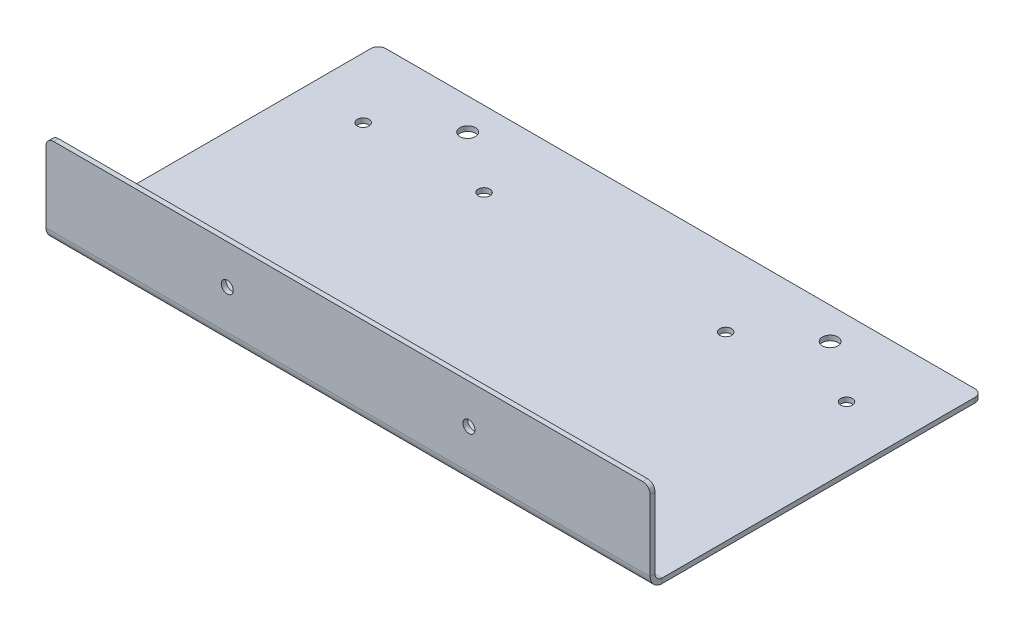
SolidWorks part; units mm, degrees
note: The reader was unsure of these and kept them because the rebuilt part matched: flange length of "Edge-Flange1".
material "5052-O"
ref_plane "Front Plane" through (0, 0, 0) normal (0, 0, 1) x (1, 0, 0)
ref_plane "Top Plane" through (0, 0, 0) normal (0, 1, 0) x (1, 0, 0)
ref_plane "Right Plane" through (0, 0, 0) normal (1, 0, 0) x (0, 0, -1)
sketch "Sketch1" plane through (0, 0, 0) normal (0, 1, 0) x (1, 0, 0)
  line L1 (0, 0) -> (254, 0)
  line L2 (0, 0) -> (0, 139.7)
  line L3 (0, 139.7) -> (254, 139.7)
  line L4 (254, 0) -> (254, 139.7)
  dimension "D1" = 139.7
  dimension "D2" = 254
base flange "Base-Flange1" sketch "Sketch1" thickness 2.0526 reverse thickness direction no parameters "D1"=3
edge flange "Edge-Flange1" sketch "Sketch8" flange angle 90 flange length 38.1 flange position material inside bend radius 3 thickness 2.0526 relief rectangular parameters "D1"=3.175, "D6"=10
sketch "Sketch8" plane through (0, 0, 0) normal (0, 0, 1) x (1, 0, 0)
  line L0 (0, 0) -> (254, 0) construction
  line L1 (0, 0) -> (254, 0)
  line L2 (0, 0) -> (0, 36.0474)
  line L3 (0, 36.0474) -> (254, 36.0474)
  line L4 (254, 36.0474) -> (254, 0)
bend "EdgeBend1" bend radius 3 bend angle 90 parameters "D5"=1
hole_wizard "#8 (0.199) Diameter Hole1" positions "Sketch9" profile "Sketch10" hole size "#8" standard "ANSI Inch" end condition through all
sketch "Sketch9" plane through (0, 0, -2.0526) normal (0, 0, -1) x (-1, 0, 0)
  line L0 (0, 19.5237) -> (-254, 19.5237) construction
  line L1 (0, 36.0474) -> (0, 3) construction
  line L2 (-254, 3) -> (-254, 36.0474) construction
  point P0 (-177.8, 19.5237)
  point P2 (-76.2, 19.5237)
  dimension "D1" = 76.2
  dimension "D2" = 76.2
sketch "Sketch10" plane through (177.8, 19.5237, -2.0526) normal (1, 0, 0) x (0, 1, 0)
  line L0 (0, 0) -> (0, 2.0526)
  line L1 (0, 2.0526) -> (2.5273, 2.0526)
  line L2 (2.5273, 2.0526) -> (2.5273, 0)
  line L5 (2.5273, 0) -> (0, 0)
  line L11 (0, -6.35) -> (0, 107.95) construction
  dimension "Thru Hole Dia." = 5.0546
  dimension "Thru Hole Depth" = 2.0526
hole_wizard "#10 (0.1935) Diameter Hole1" positions "Sketch11" profile "Sketch12" hole size "#10" standard "ANSI Inch" end condition through all
sketch "Sketch11" plane through (0, 0, 0) normal (0, 1, 0) x (1, 0, 0)
  line L0 (0, 107.95) -> (254, 107.95) construction
  line L1 (0, 139.7) -> (0, 5.0526) construction
  line L2 (254, 5.0526) -> (254, 139.7) construction
  line L4 (254, 139.7) -> (0, 139.7) construction
  line L5 (127, 139.7) -> (127, 127.3255) construction
  point P0 (25.4, 107.95)
  point P2 (76.2, 107.95)
  point P4 (177.8, 107.95)
  point P6 (228.6, 107.95)
  dimension "D1" = 31.75
  dimension "D2" = 25.4
  dimension "D3" = 25.4
  dimension "D4" = 50.8
  dimension "D5" = 50.8
sketch "Sketch12" plane through (25.4, 0, -107.95) normal (1, 0, 0) x (0, 0, 1)
  line L0 (0, 0) -> (0, 2.0526)
  line L1 (0, 2.0526) -> (2.4574, 2.0526)
  line L2 (2.4574, 2.0526) -> (2.4574, 0)
  line L5 (2.4574, 0) -> (0, 0)
  line L11 (0, -6.35) -> (0, 107.95) construction
  dimension "Thru Hole Dia." = 4.9149
  dimension "Thru Hole Depth" = 2.0526
hole_wizard "F (0.257) Diameter Hole1" positions "Sketch13" profile "Sketch14" hole size "F" standard "ANSI Inch" end condition through all
sketch "Sketch13" plane through (0, 0, 0) normal (0, 1, 0) x (1, 0, 0)
  line L0 (254, 139.7) -> (0, 139.7) construction
  line L1 (254, 5.0526) -> (254, 139.7) construction
  line L2 (0, 139.7) -> (0, 5.0526) construction
  point P0 (203.2, 126.4818)
  point P7 (50.8, 126.4818)
  point P10 (0, 0)
  dimension "D1" = 13.2182
  dimension "D2" = 50.8
  dimension "D3" = 50.8
sketch "Sketch14" plane through (203.2, 0, -126.4818) normal (1, 0, 0) x (0, 0, 1)
  line L0 (0, 0) -> (0, 2.0526)
  line L1 (0, 2.0526) -> (3.2639, 2.0526)
  line L2 (3.2639, 2.0526) -> (3.2639, 0)
  line L5 (3.2639, 0) -> (0, 0)
  line L11 (0, -6.35) -> (0, 107.95) construction
  dimension "Thru Hole Dia." = 6.5278
  dimension "Thru Hole Depth" = 2.0526
fillet "Fillet1" radius 3.175 4 edges at (254, 36.0474, -1.0263) (254, -1.0263, -139.7) (0, -1.0263, -139.7) (0, 36.0474, -1.0263)
sketch "Bend-Lines1" [suppressed] plane through (0, 0, 0) normal (0, 1, 0) x (1, 0, 0)
sketch "Bounding-Box1" [suppressed] plane through (0, 0, 0) normal (0, 1, 0) x (1, 0, 0)
sheet metal parameters "Sheet-Metal1" thickness 2.0526 parameters "D1"=3.175
flat pattern "Flat-Pattern1" [suppressed]
sketch "Bend-Lines2" plane through (0, 0, 0) normal (0, 1, 0) x (1, 0, 0)
sketch3d "Bounding-Box2" [suppressed]
  line L0 (-254, 152.4, 0) -> (0, 152.4, 0) construction
  line L1 (-254, 0, 0) -> (0, 0, 0) construction
  line L2 (-254, 152.4, 0) -> (-254, 0, 0) construction
  line L3 (0, 152.4, 0) -> (0, 0, 0) construction
sheet metal parameters "Sheet-Metal2" thickness 2.0526 parameters "D1"=3.175
flat pattern "Flat-Pattern1"
sketch "Bend-Lines2" plane through (0, 0, 0) normal (0, 1, 0) x (1, 0, 0)
  line L0 (0, 2.2949) -> (254, 2.2949) construction
  line L1 (0, 2.2949) -> (254, 2.2949) construction
sketch3d "Bounding-Box2" [suppressed]
  line L0 (254, 168.275, 0) -> (0, 168.275, 0) construction
  line L1 (254, -33.5103, 0) -> (0, -33.5103, 0) construction
  line L2 (254, 168.275, 0) -> (254, -33.5103, 0) construction
  line L3 (0, 168.275, 0) -> (0, -33.5103, 0) construction
bend of the flat pattern "Flatten-<EdgeBend1>1"
sheet metal parameters "Sheet-Metal3" thickness 2.0526 parameters "D1"=3.175
flat pattern "Flat-Pattern1"
sketch "Bend-Lines2" plane through (0, 0, 0) normal (0, 1, 0) x (1, 0, 0)
  line L0 (0, 2.2949) -> (254, 2.2949) construction
  line L1 (0, 2.2949) -> (254, 2.2949) construction
sketch3d "Bounding-Box2" [suppressed]
  line L0 (254, 168.275, 0) -> (0, 168.275, 0) construction
  line L1 (254, -33.5103, 0) -> (0, -33.5103, 0) construction
  line L2 (254, 168.275, 0) -> (254, -33.5103, 0) construction
  line L3 (0, 168.275, 0) -> (0, -33.5103, 0) construction
bend of the flat pattern "Flatten-<EdgeBend1>1"
sheet metal parameters "Sheet-Metal4" thickness 2.0526 parameters "D1"=3.175
flat pattern "Flat-Pattern1"
sketch "Bend-Lines2" plane through (0, 0, 0) normal (0, 1, 0) x (1, 0, 0)
  line L0 (0, 2.2949) -> (254, 2.2949) construction
  line L1 (0, 2.2949) -> (254, 2.2949) construction
sketch3d "Bounding-Box2" [suppressed]
  line L0 (254, 139.7, 0) -> (0, 139.7, 0) construction
  line L1 (254, -33.5103, 0) -> (0, -33.5103, 0) construction
  line L2 (254, 139.7, 0) -> (254, -33.5103, 0) construction
  line L3 (0, 139.7, 0) -> (0, -33.5103, 0) construction
bend of the flat pattern "Flatten-<EdgeBend1>1"
sheet metal parameters "Sheet-Metal5" thickness 2.0526 parameters "D1"=3.175
flat pattern "Flat-Pattern1"
sketch "Bend-Lines2" plane through (0, 0, 0) normal (0, 1, 0) x (1, 0, 0)
  line L0 (0, 1.8903) -> (254, 1.8903) construction
  line L1 (0, 1.8903) -> (254, 1.8903) construction
sketch3d "Bounding-Box2" [suppressed]
  line L0 (254, 139.7, 0) -> (0, 139.7, 0) construction
  line L1 (254, -34.3193, 0) -> (0, -34.3193, 0) construction
  line L2 (254, 139.7, 0) -> (254, -34.3193, 0) construction
  line L3 (0, 139.7, 0) -> (0, -34.3193, 0) construction
bend of the flat pattern "Flatten-<EdgeBend1>1"
equation "\"D3@Sketch13\"=\"D2@Sketch13\""
